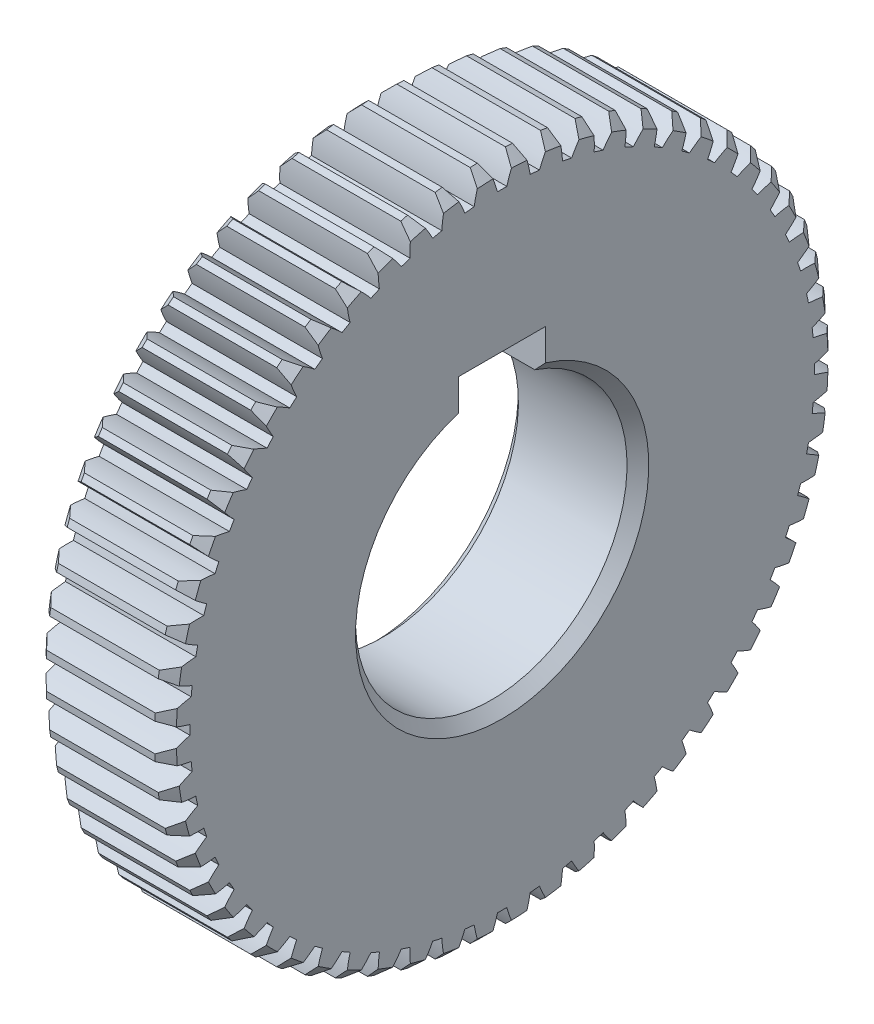
SolidWorks part; units mm, degrees
ref_plane "Plane1" through (0, 0, 0) normal (0, 0, 1) x (1, 0, 0)
ref_plane "Plane2" through (0, 0, 0) normal (0, 1, 0) x (1, 0, 0)
ref_plane "Plane3" through (0, 0, 0) normal (1, 0, 0) x (0, 0, -1)
sketch "HoldingSke" plane through (0, 0, 0) normal (0, 1, 0) x (1, 0, 0)
  line L0 (0, 0) -> (0.5, -0.866)
  line L1 (-15, 0) -> (100, 0) construction
  line L2 (0, 0) -> (-2.1039, 2.3779)
  line L3 (0, 0) -> (-11.863, 4.5341)
  line L4 (0, 0) -> (4.318, 7.479)
  line L5 (0, 0) -> (-46.8476, -17.4728)
  line L6 (0, 0) -> (-9.9476, -6.7116)
  line L7 (-2.1039, 2.3779) -> (8.6586, 51.2059)
  line L8 (-76.2, 54.61) -> (-72.9, 54.61)
  line L9 (-71.009, 38.7566) -> (-53.1078, 45.2721)
  line L10 (-76.2, 71.12) -> (104.1128, 71.12)
  line L11 (0, 0) -> (-12, 0)
  line L12 (-76.2, 101.6) -> (-76.162, 101.6)
  line L13 (24.9733, 27.94) -> (52.9518, 28.4284)
  line L14 (24.9733, 27.94) -> (24.9743, 27.94)
  line L15 (24.9733, 27.94) -> (100.4006, 29.5858)
  line L16 (-63.627, -1) -> (-12.827, -1)
  circle A0 centre (0, 0) radius 12.5
  circle A1 centre (0, 0) radius 28.749
  circle A2 centre (0, 0) radius 37.5
  circle A3 centre (0, 0) radius 12.5
  dimension "Num_teeth" = 60
  dimension "Pitch_radius" = 180.3128
  dimension "Width" = 12
  dimension "Thickness" = 12
sketch "BasProSke" plane through (0, 0, 0) normal (0, 1, 0) x (1, 0, 0)
  line L0 (-10, 0) -> (60, 0) construction
  line L1 (0, 0) -> (0, 31)
  line L2 (0, 0) -> (12, 0)
  line L3 (12, 0) -> (12, 31)
  line L4 (12, 31) -> (0, 31)
  dimension "Thickness" = 12
  dimension "Diameter" = 62
revolve "Base-Revolve" add sketch "BasProSke" angle 360 about L0
sketch "TooCutSke" plane through (0, 0, 0) normal (1, 0, 0) x (0, 0, -1)
  line L1 (0, 0) -> (0, 107) construction
  line L2 (0, 0) -> (-0.8518, 29.9879) construction
  line L3 (0, 0) -> (-3.1393, 59.9006) construction
  line L4 (-0.8518, 29.9879) -> (-1.5696, 29.9503) construction
  arc A0 (0.4302, 28.7458) -> (-0.4302, 28.7458) centre (0, 0) ccw
  arc A1 (1.3127, 30.9976) -> (-1.3127, 30.9976) centre (0, 0) ccw
  circle A2 centre (0, 0) radius 30 construction
  circle A3 centre (0, 0) radius 28.1908 construction
  arc A4 (-0.4302, 28.7458) -> (-1.3127, 30.9976) centre (-11.9871, 25.5153) ccw
  arc A5 (1.3127, 30.9976) -> (0.4302, 28.7458) centre (11.9871, 25.5153) ccw
extrude "ToothCut" cut sketch "TooCutSke" along normal through all
fillet "Breaks" [suppressed] radius 0.02
fillet "RootFillets" [suppressed] radius 0.251
pattern_circular "TeethCuts" count 60 every 6 about axis through (-10, 0, 0) along (1, 0, 0) of "ToothCut", "RootFillets", "Breaks"
sketch "HubNeaOneSke" plane through (0, 0, 0) normal (-1, 0, 0) x (0, 0, 1)
  circle A0 centre (0, 0) radius 28.749
  dimension "Diameter" = 57.498
extrude "HubNearOne" [suppressed] add sketch "HubNeaOneSke" along normal blind 38.0001
sketch "HubNeaBotSke" plane through (0, 0, 0) normal (-1, 0, 0) x (0, 0, 1)
  circle A0 centre (0, 0) radius 28.749
  dimension "Diameter" = 57.498
extrude "HubNearBoth" [suppressed] add sketch "HubNeaBotSke" along normal blind 19
ref_plane "FarPln" through (12, 0, 0) normal (1, 0, 0) x (0, 0, -1)
sketch "HubFarSke" plane through (12, 0, 0) normal (1, 0, 0) x (0, 0, -1)
  circle A0 centre (0, 0) radius 28.749
  dimension "Diameter" = 57.498
extrude "HubFar" [suppressed] add sketch "HubFarSke" along normal blind 19
sketch "BorSke" plane through (0, 0, 0) normal (1, 0, 0) x (0, 0, -1)
  circle A0 centre (0, 0) radius 12.5
  dimension "Diameter" = 25
extrude "Bore" cut sketch "BorSke" along normal mid plane 100.0001
sketch "KeySke" plane through (0, 0, 0) normal (1, 0, 0) x (0, 0, -1)
  line L0 (-4, 0) -> (-4, 15.8)
  line L1 (-4, 15.8) -> (4, 15.8)
  line L2 (4, 15.8) -> (4, 0)
  line L3 (0, 0) -> (0, 34) construction
  line L4 (-4, 0) -> (4, 0)
  dimension "Width" = 8
extrude "Keyway" cut sketch "KeySke" along normal mid plane 100.0001
pattern_circular "Keyway2" [suppressed] count 2 every 90 about axis through (-10, 0, 0) along (1, 0, 0)
chamfer "Chamfer1" distance 1 angle 45 122 edges at (12, -12.5, 0) (12, -27.6212, 14.0737) (12, -28.941, 11.1094) (12, -29.9437, 8.0234) (12, -30.6183, 4.8495) (12, -30.9575, 1.6224) (12, -28.941, -11.1094) (12, -30.9575, -1.6224) (12, -30.6183, -4.8495) (12, -29.9437, -8.0234) (12, -27.6212, -14.0737) (12, -25.9988, -16.8838) (12, -24.0915, -19.5089) (12, -21.9203, -21.9203) (12, -19.5089, -24.0915) (12, -16.8838, -25.9988) (12, -14.0737, -27.6212) (12, -11.1094, -28.941) (12, -8.0234, -29.9437) (12, -4.8495, -30.6183) (12, -1.6224, -30.9575) (12, 1.6224, -30.9575) (12, 4.8495, -30.6183) (12, 8.0234, -29.9437) (12, 11.1094, -28.941) (12, 14.0737, -27.6212) (12, 16.8838, -25.9988) (12, 19.5089, -24.0915) (12, 21.9203, -21.9203) (12, 24.0915, -19.5089) (12, 25.9988, -16.8838) (12, 27.6212, -14.0737) (12, 28.941, -11.1094) (12, 29.9437, -8.0234) (12, 30.6183, -4.8495) (12, 30.9575, -1.6224) (12, 30.9575, 1.6224) (12, 30.6183, 4.8495) (12, 29.9437, 8.0234) (12, 28.941, 11.1094) (12, 27.6212, 14.0737) (12, 25.9988, 16.8838) (12, 24.0915, 19.5089) (12, 21.9203, 21.9203) (12, 19.5089, 24.0915) (12, 16.8838, 25.9988) (12, 14.0737, 27.6212) (12, 11.1094, 28.941) (12, 8.0234, 29.9437) (12, 4.8495, 30.6183) (12, 1.6224, 30.9575) (12, -25.9988, 16.8838) (12, -24.0915, 19.5089) (12, -21.9203, 21.9203) (12, -19.5089, 24.0915) (12, -16.8838, 25.9988) (12, -1.6224, 30.9575) (12, -4.8495, 30.6183) (12, -8.0234, 29.9437) (12, -14.0737, 27.6212) (12, -11.1094, 28.941) (0, 28.941, 11.1094) (0, 29.9437, 8.0234) (0, 30.6183, 4.8495) (0, 30.9575, 1.6224) (0, 27.6212, 14.0737) (0, 25.9988, 16.8838) (0, 24.0915, 19.5089) (0, 21.9203, 21.9203) (0, 19.5089, 24.0915) (0, 16.8838, 25.9988) (0, 14.0737, 27.6212) (0, 11.1094, 28.941) (0, 8.0234, 29.9437) (0, 4.8495, 30.6183) (0, 1.6224, 30.9575) (0, -1.6224, 30.9575) (0, -4.8495, 30.6183) (0, -8.0234, 29.9437) (0, -11.1094, 28.941) (0, -14.0737, 27.6212) (0, -16.8838, 25.9988) (0, -19.5089, 24.0915) (0, -21.9203, 21.9203) (0, -24.0915, 19.5089) (0, -25.9988, 16.8838) (0, -27.6212, 14.0737) (0, -28.941, 11.1094) (0, -29.9437, 8.0234) (0, -30.6183, 4.8495) (0, -30.9575, 1.6224) (0, -30.9575, -1.6224) (0, -30.6183, -4.8495) (0, -29.9437, -8.0234) (0, -28.941, -11.1094) (0, -27.6212, -14.0737) (0, -25.9988, -16.8838) (0, -24.0915, -19.5089) (0, -21.9203, -21.9203) (0, -19.5089, -24.0915) (0, -16.8838, -25.9988) (0, -14.0737, -27.6212) (0, -11.1094, -28.941) (0, -8.0234, -29.9437) (0, -4.8495, -30.6183) (0, -1.6224, -30.9575) (0, 1.6224, -30.9575) (0, 4.8495, -30.6183) (0, 8.0234, -29.9437) (0, 11.1094, -28.941) (0, 14.0737, -27.6212) (0, 16.8838, -25.9988) (0, 19.5089, -24.0915) (0, 21.9203, -21.9203) (0, 24.0915, -19.5089) (0, 25.9988, -16.8838) (0, 27.6212, -14.0737) (0, 28.941, -11.1094) (0, 29.9437, -8.0234) (0, 30.6183, -4.8495) (0, 30.9575, -1.6224) (0, -12.5, 0)
equation "' \"Module@HoldingSke\" = 6.35"
equation "' \"Num_teeth@HoldingSke\" = 12"
equation "' \"Ap@HoldingSke\" =  20"
equation "' \"Ap@HoldingSke\" = 20"
equation "' \"Width@HoldingSke\" = 0.5 * 25.4"
equation "' \"Hub_dia@HoldingSke\"= 1 * 25.4"
equation "' \"Hub_dia@HoldingSke\" = 1 * 25.4"
equation "' \"Overall_len@HoldingSke\" = 1.0 * 25.4"
equation "' \"Bore@HoldingSke\" = 0.75 * 25.4"
equation "' \"T_dim@HoldingSke\" = 0.1 * 25.4"
equation "' \"Width@KeySke\" = 0.25 * 25.4"
equation "' \"Show_teeth@HoldingSke\" = 13"
equation "' \"Backlash@HoldingSke\" = 0.009 * 25.4"
equation "' \"Addendum_fac@HoldingSke\" = 1.0"
equation "' \"Dedendum_fac@HoldingSke\" = 1.25"
equation "' \"Dedendum_add@HoldingSke\" = 0.00005 * 25.4"
equation "' \"Clearance_fac@HoldingSke\" = 0.25"
equation "\"Pitch@HoldingSke\" = 1 / \"Module@HoldingSke\""
equation "\"Overcut_dia@TooCutSke\" = (\"Num_teeth@HoldingSke\" + 2 * \"Addendum_fac@HoldingSke\") / \"Pitch@HoldingSke\" + 0.002 * 25.4"
equation "\"Pitch_dia@TooCutSke\" = \"Num_teeth@HoldingSke\" / \"Pitch@HoldingSke\""
equation "\"Base_dia@TooCutSke\" = \"Num_teeth@HoldingSke\" / \"Pitch@HoldingSke\" * cos((\"Ap@HoldingSke\"  * 3.14159265 / 180))"
equation "\"Root_dia@TooCutSke\" = (\"Num_teeth@HoldingSke\" + 2) / \"Pitch@HoldingSke\" - 2 * (\"Addendum_fac@HoldingSke\" + \"Dedendum_fac@HoldingSke\") / \"Pitch@HoldingSke\" - \"Dedendum_add@HoldingSke\" * 2"
equation "\"Half_ang@TooCutSke\" = 180 / \"Num_teeth@HoldingSke\""
equation "\"Half_CT@TooCutSke\" = \"Num_teeth@HoldingSke\" / \"Pitch@HoldingSke\" * sin((3.14159265 / 2 / \"Num_teeth@HoldingSke\")) / 2 - 7 * \"Backlash@HoldingSke\" / 4"
equation "\"Flank_rad@TooCutSke\" = \"Num_teeth@HoldingSke\" / \"Pitch@HoldingSke\" / 5"
equation "\"Radius@RootFillets\" = \"Clearance_fac@HoldingSke\" / \"Pitch@HoldingSke\" + \"Dedendum_add@HoldingSke\""
equation "\"Break_rad@Breaks\" = 0.02 / \"Pitch@HoldingSke\""
equation "\"Thickness@HoldingSke\" = \"Width@HoldingSke\""
equation "\"OAL@HoldingSke\" = \"Thickness@HoldingSke\""
equation "\"MHD@HoldingSke\" = (\"Num_teeth@HoldingSke\" + 2) / \"Pitch@HoldingSke\" - 2 * (\"Addendum_fac@HoldingSke\" + \"Dedendum_fac@HoldingSke\")  / \"Pitch@HoldingSke\" - \"Dedendum_add@HoldingSke\" * 2"
equation "\"MBD@HoldingSke\" = (\"Num_teeth@HoldingSke\" + 2) / \"Pitch@HoldingSke\" - 2 * (\"Addendum_fac@HoldingSke\" + \"Dedendum_fac@HoldingSke\")  / \"Pitch@HoldingSke\" - \"Dedendum_add@HoldingSke\" * 2 - 0.002 * 25.4"
equation "\"MHD@HoldingSke\" = ((sgn( \"MHD@HoldingSke\" - \"Hub_dia@HoldingSke\" )-1)*( \"MHD@HoldingSke\" - \"Hub_dia@HoldingSke\" ))/-2+ \"Hub_dia@HoldingSke\""
equation "\"MBD@HoldingSke\" = ((sgn( \"MBD@HoldingSke\" - \"Bore@HoldingSke\" )-1)*( \"MBD@HoldingSke\" - \"Bore@HoldingSke\" ))/-2+ \"Bore@HoldingSke\""
equation "\"OAL@HoldingSke\" = ((sgn( \"OAL@HoldingSke\" - \"Overall_len@HoldingSke\" )+1)*( \"OAL@HoldingSke\" - \"Overall_len@HoldingSke\" ))/2 + \"Overall_len@HoldingSke\" + 0.000002 * 25.4"
equation "\"Num_teeth@TeethCuts\" = int( \"Show_teeth@HoldingSke\" ) + 1"
equation "\"Num_teeth@TeethCuts\" = ((sgn( \"Num_teeth@TeethCuts\" - \"Num_teeth@HoldingSke\" )-1)*( \"Num_teeth@TeethCuts\" - \"Num_teeth@HoldingSke\" ))/-2+ \"Num_teeth@HoldingSke\""
equation "\"Num_teeth@TeethCuts\" = ((sgn( \"Num_teeth@TeethCuts\" - 2.0)+1)*( \"Num_teeth@TeethCuts\" - 2.0))/2 +2.0"
equation "\"Angle@TeethCuts\" = 360.0 / \"Num_teeth@HoldingSke\""
equation "\"Diameter@BasProSke\" = (\"Num_teeth@HoldingSke\" + 2 * \"Addendum_fac@HoldingSke\") / \"Pitch@HoldingSke\""
equation "\"Thickness@BasProSke\"  = \"Thickness@HoldingSke\""
equation "' \"Fillet_rad@BasProSke\" =  \"Thickness@HoldingSke\" * 0.05"
equation "' \"Fillet_rad@BasProSke\" = \"Thickness@HoldingSke\" * 0.05"
equation "\"MHD@HoldingSke\" = ((sgn( \"MHD@HoldingSke\" - \"Root_dia@TooCutSke\" )-1)*( \"MHD@HoldingSke\" - \"Root_dia@TooCutSke\" ))/-2+ \"Root_dia@TooCutSke\""
equation "\"Diameter@HubNeaOneSke\" = \"MHD@HoldingSke\""
equation "\"Length@HubNearOne\" = \"OAL@HoldingSke\" - \"Thickness@BasProSke\""
equation "\"Diameter@HubNeaBotSke\" = \"MHD@HoldingSke\""
equation "\"Length@HubNearBoth\" = ( \"OAL@HoldingSke\" - \"Thickness@BasProSke\" ) / 2.0"
equation "\"Thickness@FarPln\" = \"Thickness@BasProSke\""
equation "\"Diameter@HubFarSke\" = \"MHD@HoldingSke\""
equation "\"Length@HubFar\" = ( \"OAL@HoldingSke\" - \"Thickness@BasProSke\" ) / 2.0"
equation "\"Diameter@BorSke\" = \"MBD@HoldingSke\""
equation "\"D1@Bore\" = \"OAL@HoldingSke\" * 2.0"
equation "\"D1@Keyway\" = \"OAL@HoldingSke\" * 2.0"
equation "\"Offset@KeySke\" = \"T_dim@HoldingSke\" + \"MBD@HoldingSke\" / 2.0"
